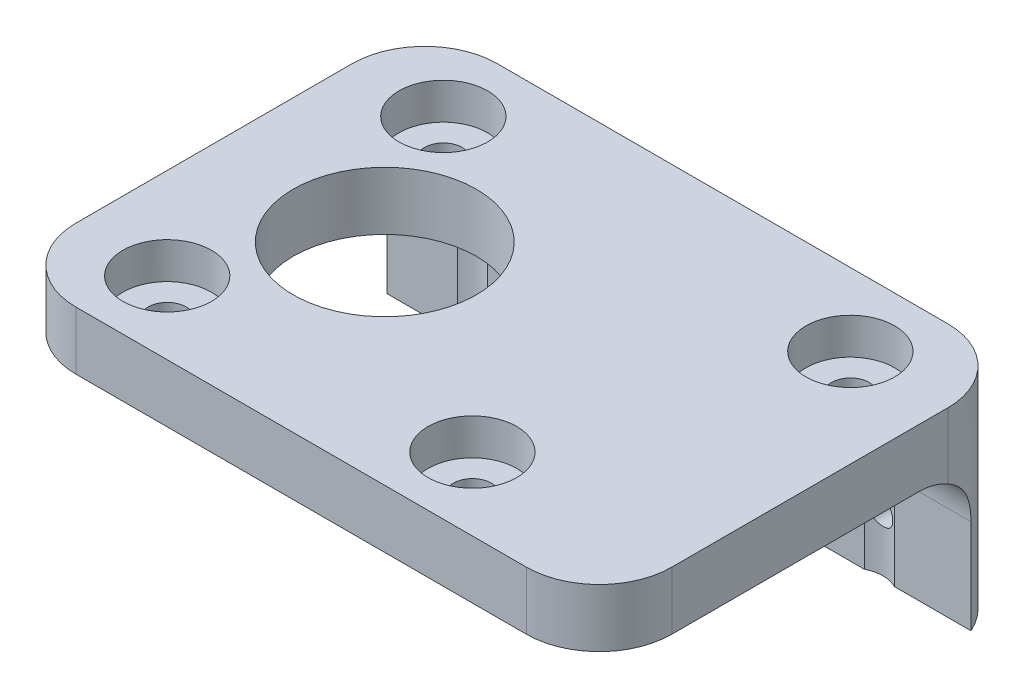
SolidWorks part; units mm, degrees
ref_plane "Front Plane" through (0, 0, 0) normal (0, 0, 1) x (1, 0, 0)
ref_plane "Top Plane" through (0, 0, 0) normal (0, 1, 0) x (1, 0, 0)
ref_plane "Right Plane" through (0, 0, 0) normal (1, 0, 0) x (0, 0, -1)
sketch "Sketch1" plane through (0, 0, 0) normal (0, 1, 0) x (1, 0, 0)
  line L1 (0, 0) -> (82, 0)
  line L2 (0, 0) -> (0, 58)
  line L3 (0, 58) -> (82, 58)
  line L4 (82, 0) -> (82, 58)
  line L5 (0, 58) -> (82, 58) construction
  line L6 (0, 58) -> (0, 118.9)
  line L7 (0, 29) -> (82, 29) construction
  line L8 (0, 118.9) -> (82, 118.9)
  line L9 (0, 48) -> (82, 48) construction
  line L10 (82, 58) -> (82, 118.9)
  line L11 (0, 10) -> (82, 10) construction
  circle A4 centre (12.5611, 48) radius 6.1
  circle A5 centre (12.5611, 10) radius 6.1
  circle A6 centre (54.5611, 10) radius 6.1
  circle A7 centre (68.57, 48) radius 6.1
  circle A8 centre (23.5, 29) radius 12.6
  dimension "D10" = 12.2
  dimension "D12" = 42
  dimension "D13" = 40.5
  dimension "D14" = 25.2
  dimension "D15" = 23.5
  dimension "D16" = 45.07
  dimension "D1" = 58
  dimension "D2" = 82
  dimension "D3" = 60.9
  dimension "D8" = 38
  dimension "D9" = 19
extrude "Boss-Extrude1" add sketch "Sketch1" along normal blind 5 contours L1 L4 L3 L2 A8 A7 A6 A5 A4 region at (43.7889, 0, -29)
sketch "Sketch2" plane through (0, 5, 0) normal (0, 1, 0) x (1, 0, 0)
  line L8 (0, 0) -> (82, 0)
  line L9 (0, 0) -> (0, 58)
  line L10 (0, 58) -> (82, 58)
  line L11 (82, 0) -> (82, 58)
  circle A0 centre (12.5611, 48) radius 2.6
  circle A1 centre (68.57, 48) radius 2.6
  circle A2 centre (54.5611, 10) radius 2.6
  circle A3 centre (12.5611, 10) radius 2.6
  circle A4 centre (23.5, 29) radius 12.6
  circle A5 centre (23.5, 29) radius 12.6 construction
  dimension "D1" = 5.2
extrude "Boss-Extrude3" add sketch "Sketch2" along normal blind 3
sketch "Sketch3" plane through (0, 8, 0) normal (0, 1, 0) x (1, 0, 0)
  line L0 (82, 58) -> (0, 58) construction
  line L1 (0, 58) -> (82, 58)
  line L2 (0, 58) -> (0, 52)
  line L3 (0, 52) -> (82, 52)
  line L4 (82, 58) -> (82, 52)
  line L5 (0, 58) -> (0, 0) construction
  line L7 (82, 0) -> (82, 58) construction
  dimension "D1" = 6
extrude "Boss-Extrude4" add sketch "Sketch3" along normal blind 21
fillet "Fillet7" radius 5 1 edges at (41, 8, -52)
sketch "Sketch6" plane through (0, 8, 0) normal (0, 1, 0) x (1, 0, 0)
  circle A0 centre (12.5611, 48) radius 4.5
  circle A1 centre (68.57, 48) radius 4.5
  dimension "D1" = 9
extrude "Cut-Extrude1" cut sketch "Sketch6" along normal through all
sketch "Sketch8" plane through (0, 8, 0) normal (0, 1, 0) x (1, 0, 0)
  line L0 (0, 23.5) -> (82, 23.5)
  line L1 (0, 47) -> (0, 0) construction
  line L2 (82, 0) -> (82, 47) construction
ref_plane "Plane1" through (0, 0, -28.5) normal (0, 0, 1) x (1, 0, 0)
sketch "Sketch9" plane through (0, 8, 0) normal (0, 1, 0) x (1, 0, 0)
  line L0 (82, 0) -> (82, 47) construction
  line L1 (0, 0) -> (82, 0)
  line L2 (0, 0) -> (0, 6)
  line L3 (0, 6) -> (82, 6)
  line L4 (82, 0) -> (82, 6)
  dimension "D1" = 6
extrude "Boss-Extrude6" add sketch "Sketch9" along normal up to surface (21 mm away) up to face at (40.7828, 29, -53.625)
fillet "Fillet9" radius 8 1 edges at (41, 8, -6)
sketch "Sketch11" plane through (0, 8, 0) normal (0, 1, 0) x (1, 0, 0)
  circle A0 centre (12.5611, 10) radius 4.5
  circle A1 centre (54.5611, 10) radius 4.5
  dimension "D1" = 9
extrude "Cut-Extrude3" cut sketch "Sketch11" along normal through all
sketch "Sketch12" plane through (0, 8, 0) normal (0, 1, 0) x (1, 0, 0)
  line L0 (0, 47) -> (0, 14) construction
  line L1 (0, 47) -> (82, 47)
  line L2 (0, 47) -> (0, 58)
  line L3 (0, 58) -> (82, 58)
  line L4 (82, 47) -> (82, 58)
  line L5 (82, 14) -> (82, 47) construction
  line L6 (82, 58) -> (0, 58) construction
  line L7 (8.1736, 47) -> (0, 47) construction
extrude "Cut-Extrude4" cut sketch "Sketch12" along normal through all
mirror "Mirror1" about plane through (0, 0, 0) normal (0, 1, 0) of bodies 117
sketch "Sketch13" plane through (0, 29, 0) normal (0, 1, 0) x (1, 0, 0)
  line L1 (0, 0) -> (82, 0)
  line L2 (0, 0) -> (0, 58)
  line L3 (0, 58) -> (82, 58)
  line L4 (82, 0) -> (82, 58)
  line L5 (82, 14) -> (82, 58) construction
  line L6 (82, 58) -> (0, 58) construction
extrude "Cut-Extrude5" cut sketch "Sketch13" against normal blind 29
sketch "Sketch14" plane through (0, -8, 0) normal (0, -1, 0) x (1, 0, 0)
  line L0 (82, -58) -> (0, -58) construction
  line L1 (0, -58) -> (82, -58)
  line L2 (0, -58) -> (0, -52)
  line L3 (0, -52) -> (82, -52)
  line L4 (82, -58) -> (82, -52)
  line L5 (82, -14) -> (82, -58) construction
  line L6 (0, -58) -> (0, -14) construction
  dimension "D1" = 6
extrude "Boss-Extrude7" add sketch "Sketch14" along normal up to surface (21 mm away) up to face at (37.2805, -29, -4.375)
fillet "Fillet10" radius 8 1 edges at (41, -8, -52)
sketch "Sketch15" plane through (0, -8, 0) normal (0, -1, 0) x (1, 0, 0)
  circle A0 centre (12.5611, -48) radius 4.5
  circle A1 centre (68.57, -48) radius 4.5
  dimension "D1" = 9
extrude "Cut-Extrude6" cut sketch "Sketch15" along normal through all
sketch "Sketch16" plane through (0, -8, 0) normal (0, -1, 0) x (1, 0, 0)
  line L1 (0, -14) -> (82, -14)
  line L2 (0, -14) -> (0, 0)
  line L3 (0, 0) -> (82, 0)
  line L4 (82, -14) -> (82, 0)
extrude "Cut-Extrude7" cut sketch "Sketch16" along normal through all
fillet "Fillet11" radius 10 4 edges at (82, -14.5, -58) (0, -14.5, -58) (0, -4, 0) (82, -4, 0)
sketch "Sketch17" plane through (0, 0, -58) normal (0, 0, -1) x (-1, 0, 0)
  circle A0 centre (-23.6, -21.5) radius 1.6
  circle A1 centre (-68.6, -21.5) radius 1.6
  circle A2 centre (-23.6, -21.5) radius 1.6 construction
  circle A3 centre (-68.6, -21.5) radius 1.6 construction
extrude "Cut-Extrude8" cut sketch "Sketch17" against normal through all
